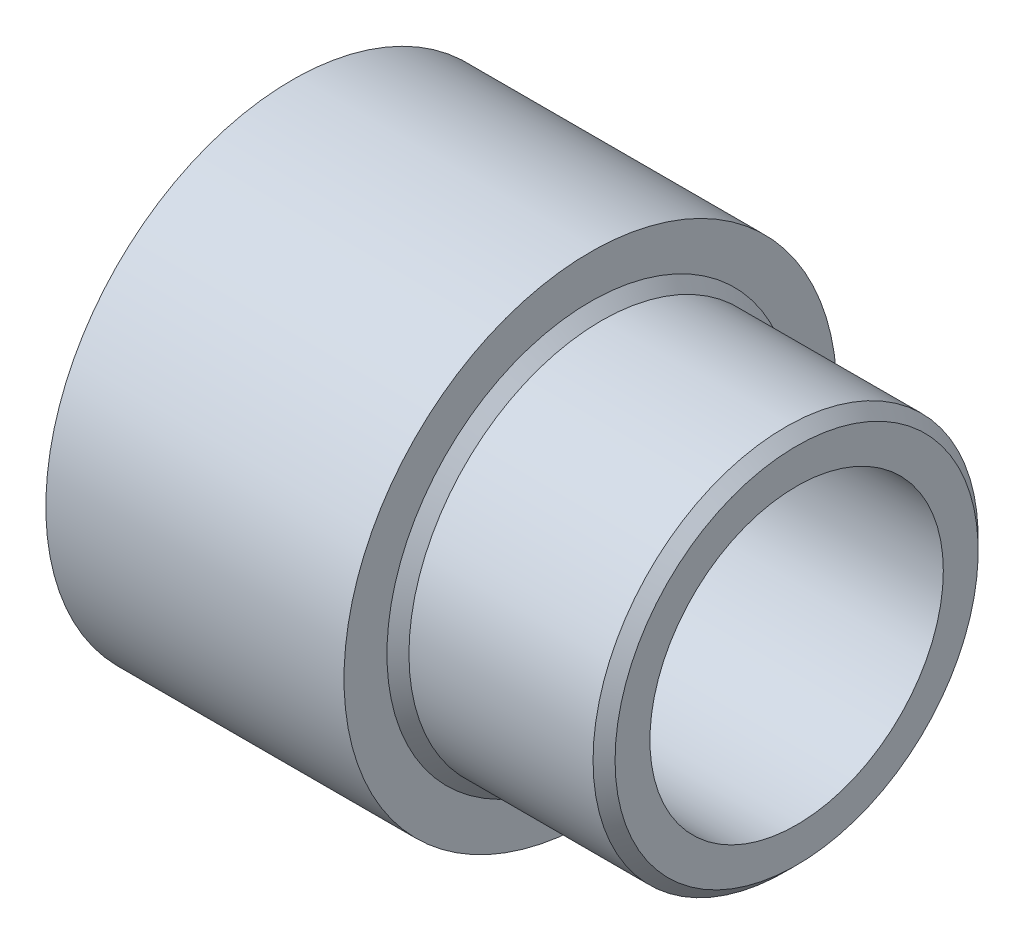
SolidWorks part; units mm, degrees
material "PVC Rigid"
ref_plane "Front" through (0, 0, 0) normal (0, 0, 1) x (1, 0, 0)
ref_plane "Top" through (0, 0, 0) normal (0, 1, 0) x (1, 0, 0)
ref_plane "Right" through (0, 0, 0) normal (1, 0, 0) x (0, 0, -1)
sketch "Sketch1" plane through (0, 0, 0) normal (1, 0, 0) x (0, 0, -1)
  circle A0 centre (0, 0) radius 17.0688
  dimension "OD" = 34.1376
extrude "OD-Extrude1" add sketch "Sketch1" along normal blind 20.6502
sketch "Sketch4" plane through (20.6502, 0, 0) normal (-1, 0, 0) x (0, 0, 1)
  circle A0 centre (0, 0) radius 13.335
  dimension "MaleThdOD" = 26.67
extrude "MaleTHD-Extrude2" add sketch "Sketch4" against normal blind 14.2748
chamfer "Chamfer1" distance 0.762 angle 45 2 edges at (20.6502, 0, -13.335) (34.925, 0, 13.335)
sketch "Sketch6" plane through (0, 0, 0) normal (-1, 0, 0) x (0, 0, 1)
  circle A0 centre (0, 0) radius 13.5128
  dimension "ConduitDiaID" = 27.0256
extrude "SOCKET-Cut-Extrude1" cut sketch "Sketch6" against normal blind 19.05
sketch "Sketch7" plane through (19.05, 0, 0) normal (1, 0, 0) x (0, 0, -1)
  circle A0 centre (0, 0) radius 10.16
  dimension "ThruDIA" = 20.32
extrude "ThruDIA-Cut-Extrude2" cut sketch "Sketch7" along normal through all
other "CPoint1-conduit" parameters "Diameter"=19.05, "StubLength"=0
ref_axis "Axis1" through (9.05, 0, 0) along (1, 0, 0)
other "CPoint2-electrical" parameters "Diameter"=10, "StubLength"=0
ref_axis "Axis2" through (44.925, 0, 0) along (-1, 0, 0)
sketch3d "3DSketch4"
  point P0 (25.4087, 0, 0)
other "RPoint1"
